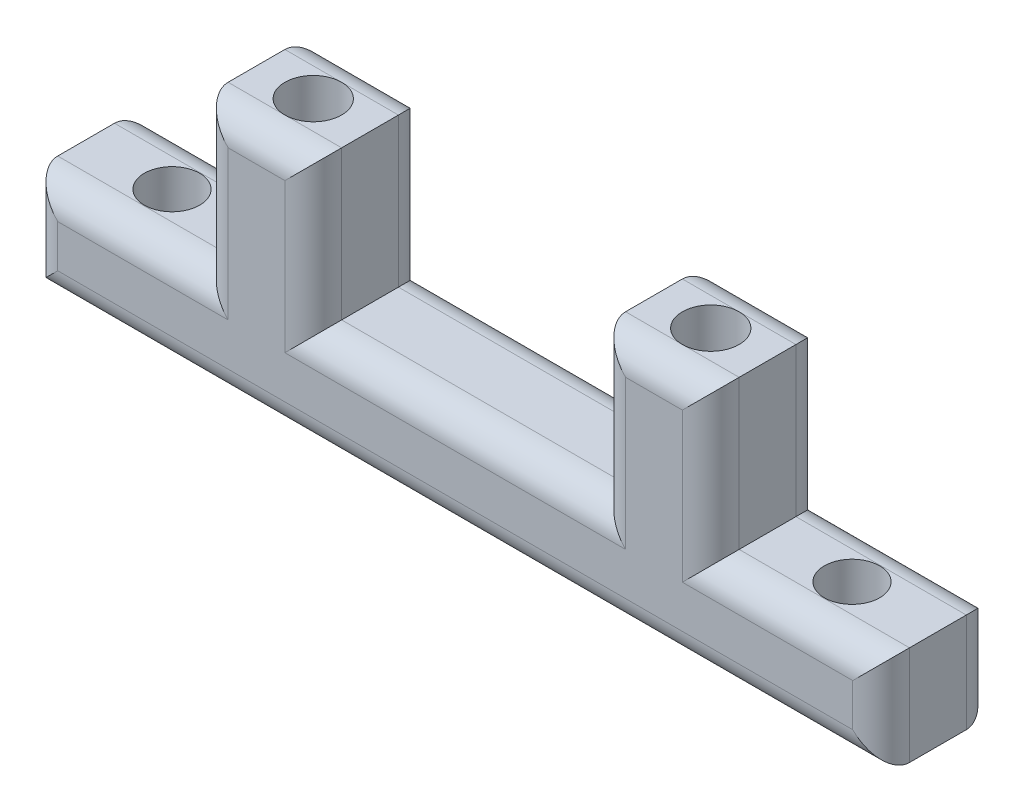
SolidWorks part; units mm, degrees
ref_plane "Front Plane" through (0, 0, 0) normal (0, 0, 1) x (1, 0, 0)
ref_plane "Top Plane" through (0, 0, 0) normal (0, 1, 0) x (1, 0, 0)
ref_plane "Right Plane" through (0, 0, 0) normal (1, 0, 0) x (0, 0, -1)
sketch "Sketch1" plane through (0, 0, 0) normal (0, 1, 0) x (1, 0, 0)
  line L1 (-30, 4) -> (30, 4)
  line L2 (-30, 4) -> (-30, -4)
  line L3 (-30, -4) -> (30, -4)
  line L4 (30, 4) -> (30, -4)
  line L5 (-30, 4) -> (30, -4) construction
  line L6 (-30, -4) -> (30, 4) construction
  point P0 (0, 0)
  dimension "D1" = 60
  dimension "D2" = 8
extrude "Boss-Extrude1" add sketch "Sketch1" along normal blind 7
sketch "Sketch2" plane through (0, 7, 0) normal (0, 1, 0) x (1, 0, 0)
  line L0 (-30, -4) -> (30, -4) construction
  line L1 (-18, 4) -> (-10, 4)
  line L2 (-18, 4) -> (-18, -4)
  line L3 (-18, -4) -> (-10, -4)
  line L4 (-10, 4) -> (-10, -4)
  line L5 (-18, 4) -> (-10, -4) construction
  line L6 (-18, -4) -> (-10, 4) construction
  line L7 (-30, 4) -> (-30, -4) construction
  line L8 (10, 4) -> (18, 4)
  line L9 (10, 4) -> (10, -4)
  line L10 (10, -4) -> (18, -4)
  line L11 (18, 4) -> (18, -4)
  line L12 (10, 4) -> (18, -4) construction
  line L13 (10, -4) -> (18, 4) construction
  line L15 (30, -4) -> (30, 4) construction
  point P0 (-14, 0)
  point P7 (14, 0)
  dimension "D1" = 8
  dimension "D2" = 8
  dimension "D3" = 20
  dimension "D4" = 12
  dimension "D5" = 12
extrude "Boss-Extrude2" add sketch "Sketch2" along normal blind 10.5
sketch "Sketch3" plane through (0, 17.5, 0) normal (0, 1, 0) x (1, 0, 0)
  line L0 (10, 4) -> (10, -4) construction
  line L2 (-18, 4) -> (-18, -4) construction
  circle A0 centre (-14, 0) radius 2
  circle A1 centre (14, 0) radius 2
  dimension "D1" = 4
  dimension "D2" = 4
  dimension "D3" = 4
  dimension "D4" = 4
extrude "Cut-Extrude1" cut sketch "Sketch3" against normal through all
sketch "Sketch5" plane through (0, 0, 0) normal (0, -1, 0) x (1, 0, 0)
  line L0 (-30, 4) -> (30, 4) construction
  circle A0 centre (-23.95, 0) radius 1.95
  circle A1 centre (23.95, 0) radius 1.95
  circle A3 centre (14, 0) radius 2 construction
  circle A5 centre (-14, 0) radius 2 construction
  dimension "D1" = 3.9
  dimension "D2" = 3.9
  dimension "D3" = 6
  dimension "D4" = 6
  dimension "D5" = 4
  dimension "D6" = 4
extrude "Cut-Extrude2" cut sketch "Sketch5" against normal through all
fillet "Fillet1" radius 2 24 edges at (30, 3.5, -4) (24, 7, -4) (18, 12.25, -4) (14, 17.5, -4) (10, 12.25, -4) (0, 7, -4) (-10, 12.25, -4) (-14, 17.5, -4) (-18, 12.25, -4) (-24, 7, -4) (-30, 3.5, -4) (0, 0, -4) (-30, 3.5, 4) (-24, 7, 4) (-18, 12.25, 4) (-14, 17.5, 4) (-10, 12.25, 4) (0, 7, 4) (10, 12.25, 4) (14, 17.5, 4) (18, 12.25, 4) (24, 7, 4) (30, 3.5, 4) (0, 0, 4)
